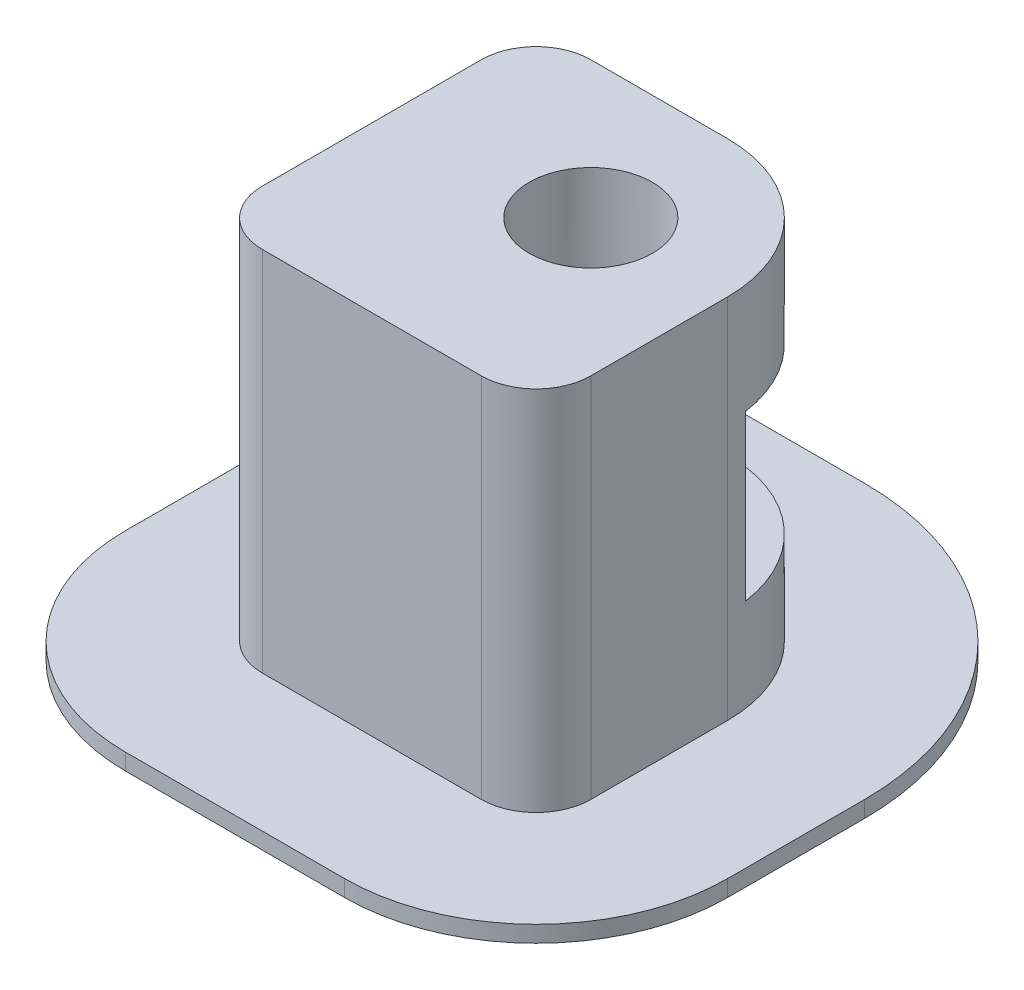
SolidWorks part; units mm, degrees
material "ABS"
ref_plane "Front Plane" through (0, 0, 0) normal (0, 0, 1) x (1, 0, 0)
ref_plane "Top Plane" through (0, 0, 0) normal (0, 1, 0) x (1, 0, 0)
ref_plane "Right Plane" through (0, 0, 0) normal (1, 0, 0) x (0, 0, -1)
sketch "Sketch1" plane through (0, 0, 0) normal (0, 1, 0) x (1, 0, 0)
  line L0 (0, 5) -> (-7, 5)
  line L1 (-7, 5) -> (-7, -7)
  line L2 (-7, -7) -> (5, -7)
  line L3 (5, -7) -> (5, 0)
  circle A0 centre (0, 0) radius 1.6
  arc A1 (5, 0) -> (0, 5) centre (0, 0) ccw
  dimension "D1" = 3.2
  dimension "D2" = 10
  dimension "D3" = 12
extrude "Boss-Extrude1" add sketch "Sketch1" along normal mid plane 14
fillet "Fillet1" radius 2 3 edges at (5, 0, 7) (-7, 0, 7) (-7, 0, -5)
sketch "Sketch2" plane through (0, 0, 0) normal (0, 1, 0) x (1, 0, 0)
  line L0 (-0.8966, 3.3461) -> (0.7574, 5)
  line L1 (-2.4495, -2.4495) -> (0.8966, -3.3461)
  line L2 (0.8966, -3.3461) -> (3.3461, -0.8966)
  line L3 (3.3461, -0.8966) -> (2.4495, 2.4495) construction
  line L4 (2.4495, 2.4495) -> (-0.8966, 3.3461) construction
  line L5 (-0.8966, 3.3461) -> (-3.3461, 0.8966)
  line L6 (-3.3461, 0.8966) -> (-2.4495, -2.4495)
  line L7 (0.7574, 5) -> (5, 5)
  line L8 (3.3461, -0.8966) -> (5, 0.7574)
  line L9 (5, 0.7574) -> (5, 5)
  line L11 (0, 0) -> (2.4495, 2.4495) construction
  line L12 (2.4495, 2.4495) -> (3.5355, 3.5355) construction
  line L13 (5, -5) -> (5, 0) construction
  circle A0 centre (0, 0) radius 3 construction
  arc A2 (5, 0) -> (0, 5) centre (0, 0) ccw construction
  dimension "D1" = 6
ref_plane "Plane1" through (0, 3, 0) normal (0, 1, 0) x (1, 0, 0)
ref_plane "Plane2" through (0, -3, 0) normal (0, -1, 0) x (-1, 0, 0)
extrude "Cut-Extrude1" cut sketch "Sketch2" against normal blind 3 from surface starting at plane "Plane1"
extrude "Cut-Extrude2" cut sketch "Sketch2<2>" along normal blind 3 from surface starting at plane "Plane2"
sketch "Sketch2<2>" plane through (0, 0, 0) normal (0, 1, 0) x (1, 0, 0) same geometry as "Sketch2"
sketch "Sketch3" plane through (0, 7, 0) normal (0, 1, 0) x (1, 0, 0)
  circle A0 centre (0, 0) radius 2.25
  dimension "D1" = 4.5
extrude "Cut-Extrude3" cut sketch "Sketch3" against normal blind 7
sketch "Sketch4" plane through (0, -7, 0) normal (0, -1, 0) x (1, 0, 0)
  line L26 (10, 0) -> (10, 5)
  line L27 (3, 12) -> (-5, 12)
  line L28 (-12, 5) -> (-12, -3)
  line L29 (-5, -10) -> (0, -10)
  line L30 (10, 0) -> (10, 5)
  line L31 (3, 12) -> (-5, 12)
  line L32 (-12, 5) -> (-12, -3)
  line L33 (-5, -10) -> (0, -10)
  circle A14 centre (0, 0) radius 1.6
  circle A15 centre (0, 0) radius 1.6 construction
  arc A18 (10, 5) -> (3, 12) centre (3, 5) ccw
  arc A19 (0, -10) -> (10, 0) centre (0, 0) ccw
  arc A20 (-12, -3) -> (-5, -10) centre (-5, -3) ccw
  arc A21 (-5, 12) -> (-12, 5) centre (-5, 5) ccw
  arc A22 (10, 5) -> (3, 12) centre (3, 5) ccw
  arc A23 (0, -10) -> (10, 0) centre (0, 0) ccw
  arc A24 (-12, -3) -> (-5, -10) centre (-5, -3) ccw
  arc A25 (-5, 12) -> (-12, 5) centre (-5, 5) ccw
  dimension "D1" = 5
extrude "Boss-Extrude3" add sketch "Sketch4" against normal blind 0.6
